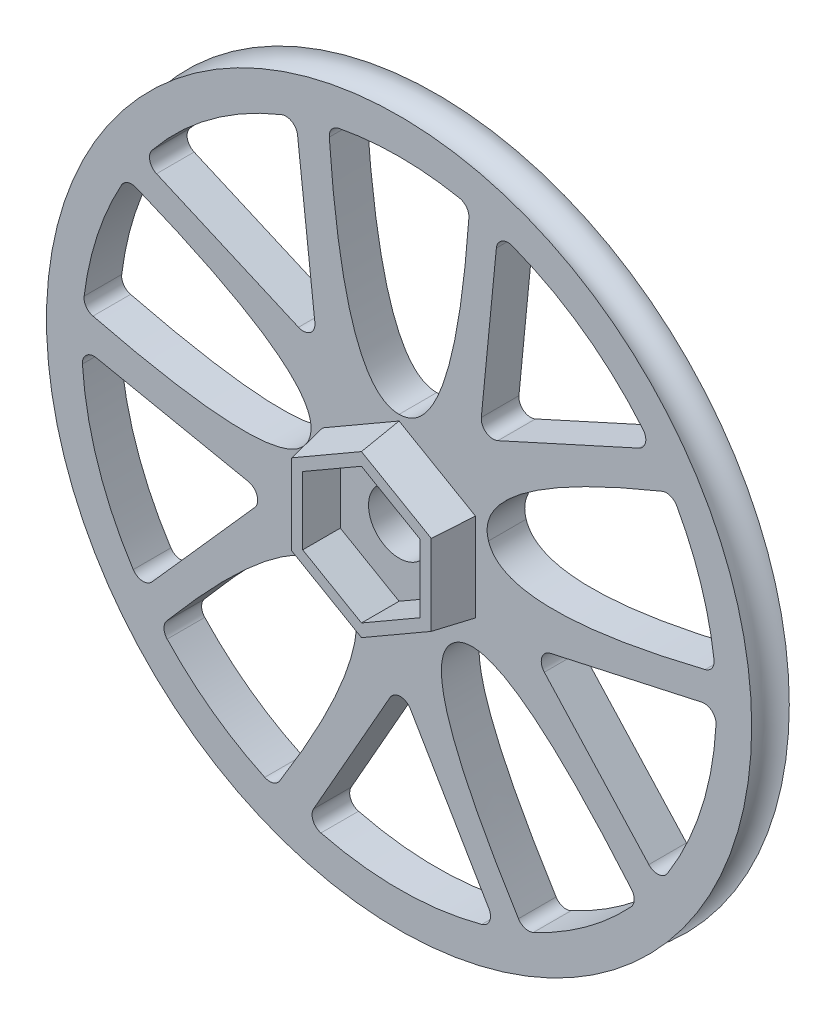
SolidWorks part; units mm, degrees
ref_plane "Front Plane" through (0, 0, 0) normal (0, 0, 1) x (1, 0, 0)
ref_plane "Top Plane" through (0, 0, 0) normal (0, 1, 0) x (1, 0, 0)
ref_plane "Right Plane" through (0, 0, 0) normal (1, 0, 0) x (0, 0, -1)
sketch "Sketch1" plane through (0, 0, 0) normal (0, 0, 1) x (1, 0, 0)
  circle A0 centre (0, 0) radius 38.1
  dimension "D1" = 76.2
extrude "Boss-Extrude1" add sketch "Sketch1" along normal mid plane 4.064
ref_axis "Axis1" through (0, 0, 17.7732) along (0, 0, -1)
sketch "Sketch2" plane through (0, 0, 0) normal (1, 0, 0) x (0, 0, -1)
  line L2 (-2.032, 38.1) -> (-2.032, -38.1) construction
  line L3 (-2.032, 38.1) -> (2.032, 38.1)
  circle A0 centre (0, 38.1) radius 2.032 construction
  arc A1 (-2.032, 38.1) -> (2.032, 38.1) centre (0, 38.1) ccw
revolve "Cut-Revolve1" cut sketch "Sketch2" angle 360 about axis through (0, 0, 17.7732) along (0, 0, -1)
sketch "Sketch3" plane through (0, 0, 0) normal (0, 0, 1) x (1, 0, 0)
  line L0 (0, 0) -> (0, 34.29) construction
  line L1 (0, 0) -> (34.29, 0) construction
  line L2 (-2.8815, 10.16) -> (2.8815, 10.16) construction
  line L3 (2.8814, 10.16) -> (-2.8815, 10.16) construction
  circle A0 centre (0, 0) radius 10.16 construction
  arc A1 (-7.62, 33.4326) -> (7.62, 33.4326) centre (0, 0) cw
  circle A2 centre (0, 0) radius 34.29 construction
  spline S0 degree 2 poles (0, 10.16) (6.0921, 10.16) (7.62, 33.4326) knots 0 0 0 1 1 1
  spline S1 degree 2 poles (0, 10.16) (-6.0921, 10.16) (-7.62, 33.4326) knots 0 0 0 1 1 1
  dimension "D1" = 20.32
  dimension "D2" = 68.58
  dimension "D3" = 15.24
extrude "Cut-Extrude1" cut sketch "Sketch3" against normal mid plane 5.08
pattern_circular "CirPattern1" count 5 over 360 about axis through (0, 0, 17.7732) along (0, 0, -1) of "Cut-Extrude1"
sketch "Sketch4" plane through (0, 0, 0) normal (0, 0, 1) x (1, 0, 0)
  line L0 (10.668, 32.5883) -> (8.6709, 12.1233)
  line L1 (8.6709, 12.1233) -> (27.3927, 20.6263)
  circle A0 centre (0, 0) radius 10.16 construction
  circle A1 centre (0, 0) radius 10.16 construction
  circle A2 centre (0, 0) radius 34.29 construction
  circle A3 centre (0, 0) radius 34.29 construction
  arc A4 (10.668, 32.5883) -> (27.3927, 20.6263) centre (0, 0) cw
  dimension "D1" = 3.048
  dimension "D2" = 3.048
  dimension "D3" = 60
extrude "Cut-Extrude2" cut sketch "Sketch4" against normal mid plane 5.08
pattern_circular "CirPattern2" count 5 over 360 about axis through (0, 0, 17.7732) along (0, 0, -1) of "Cut-Extrude2"
fillet "Fillet1" radius 1.27 25 edges at (-14.1408, -4.7113, 0) (0.1109, -14.9046, 0) (14.2094, -4.5003, 0) (8.6709, 12.1233, 0) (-8.8505, 11.9929, 0) (10.668, 32.5883, 0) (27.3927, 20.6263, 0) (34.151, 3.0842, 0) (29.4416, 17.5783, 0) (34.2899, -0.0755, 0) (28.0816, -19.6781, 0) (25.8159, -22.5686, 0) (13.4865, -31.5265, 0) (10.5243, -32.635, 0) (-10.0373, -32.788, 0) (-13.4865, -31.5265, 0) (-25.8159, -22.5686, 0) (-27.7855, -20.094, 0) (-34.285, -0.586, 0) (-34.151, 3.0842, 0) (-29.4416, 17.5783, 0) (-27.6967, 20.2162, 0) (-11.152, 32.4259, 0) (-7.62, 33.4326, 0) (7.62, 33.4326, 0)
sketch "Sketch5" plane through (0, 0, 2.032) normal (0, 0, 1) x (1, 0, 0)
  line L1 (-8.255, -4.766) -> (0, -9.5321)
  line L2 (0, -9.5321) -> (8.255, -4.766)
  line L3 (8.255, -4.766) -> (8.255, 4.766)
  line L4 (8.255, 4.766) -> (0, 9.5321)
  line L5 (0, 9.5321) -> (-8.255, 4.766)
  line L6 (-8.255, 4.766) -> (-8.255, -4.766)
  line L7 (0, 0) -> (0, 34.29) construction
  circle A0 centre (0, 0) radius 8.255 construction
  point P1 (0, 0)
  dimension "D1" = 16.51
extrude "Boss-Extrude2" add sketch "Sketch5" along normal blind 4.064 draft 10
sketch "Sketch6" plane through (0, 0, 6.096) normal (0, 0, 1) x (1, 0, 0)
  line L0 (0, 0) -> (0, 34.29) construction
  line L1 (0, -7.3323) -> (6.35, -3.6662)
  line L2 (6.35, -3.6662) -> (6.35, 3.6662)
  line L3 (6.35, 3.6662) -> (0, 7.3323)
  line L4 (0, 7.3323) -> (-6.35, 3.6662)
  line L5 (-6.35, 3.6662) -> (-6.35, -3.6662)
  line L6 (-6.35, -3.6662) -> (0, -7.3323)
  circle A0 centre (0, 0) radius 6.35 construction
  point P1 (0, 0)
  dimension "D1" = 12.7
extrude "Cut-Extrude3" cut sketch "Sketch6" against normal up to surface (4.064 mm away) up to face at (25.9693, -8.2247, 2.032)
sketch "Sketch7" plane through (0, 0, 2.032) normal (0, 0, 1) x (1, 0, 0)
  circle A0 centre (0, 0) radius 3.302
  dimension "D1" = 6.604
extrude "Cut-Extrude4" cut sketch "Sketch7" against normal up to next
